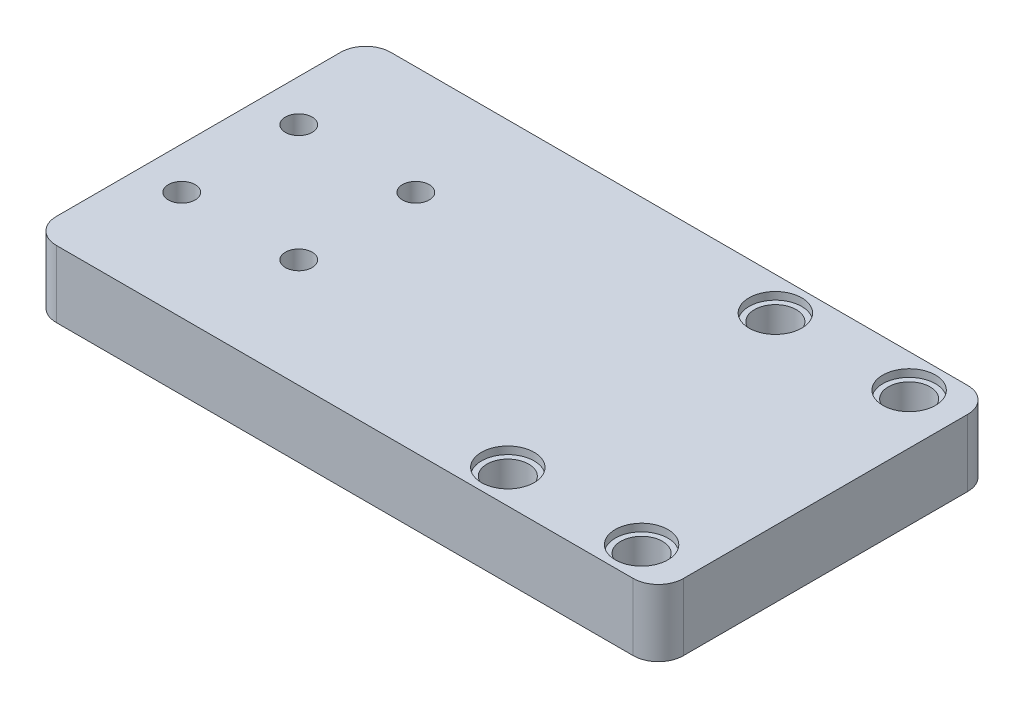
SolidWorks part; units mm, degrees
ref_plane "前视基准面" through (0, 0, 0) normal (0, 0, 1) x (1, 0, 0)
ref_plane "上视基准面" through (0, 0, 0) normal (0, 1, 0) x (1, 0, 0)
ref_plane "右视基准面" through (0, 0, 0) normal (1, 0, 0) x (0, 0, -1)
other "Configuration Table"
sketch "草图1" plane through (0, 0, 0) normal (0, 1, 0) x (1, 0, 0)
  line L1 (-37.5, -20) -> (37.5, -20)
  line L2 (-37.5, -20) -> (-37.5, 20)
  line L3 (-37.5, 20) -> (37.5, 20)
  line L4 (37.5, -20) -> (37.5, 20)
  line L5 (-37.5, -20) -> (37.5, 20) construction
  line L6 (-37.5, 20) -> (37.5, -20) construction
  point P0 (0, 0)
  dimension "D1" = 75
  dimension "D2" = 40
extrude "凸台-拉伸1" add sketch "草图1" along normal blind 8
sketch "草图2" plane through (0, 8, 0) normal (0, 1, 0) x (1, 0, 0)
  line L0 (-37.5, 20) -> (-37.5, -20) construction
  line L1 (-32.5, -7) -> (-18.5, -7) construction
  line L2 (-32.5, -7) -> (-32.5, 7) construction
  line L3 (-32.5, 7) -> (-18.5, 7) construction
  line L4 (-18.5, -7) -> (-18.5, 7) construction
  line L5 (-32.5, -7) -> (-18.5, 7) construction
  line L6 (-32.5, 7) -> (-18.5, -7) construction
  line L7 (31.5, -16) -> (15.5, -16) construction
  line L8 (31.5, -16) -> (31.5, 16) construction
  line L9 (31.5, 16) -> (15.5, 16) construction
  line L10 (15.5, -16) -> (15.5, 16) construction
  line L11 (31.5, -16) -> (15.5, 16) construction
  line L12 (31.5, 16) -> (15.5, -16) construction
  line L13 (-32.5, 7) -> (-18.5, 7) construction
  line L14 (-32.5, 7) -> (-32.5, -7) construction
  line L15 (15.5, 16) -> (31.5, 16) construction
  circle A0 centre (-32.5, 7) radius 1.6
  circle A1 centre (15.5, 16) radius 2.5
  circle A2 centre (-18.5, 7) radius 1.6
  circle A3 centre (-18.5, -7) radius 1.6
  circle A4 centre (-32.5, -7) radius 1.6
  circle A5 centre (31.5, 16) radius 2.5
  circle A6 centre (31.5, -16) radius 2.5
  circle A7 centre (15.5, -16) radius 2.5
  point P0 (-25.5, 0)
  point P2 (15.5, -15.299)
  point P5 (23.5, 0)
  point P15 (15.9941, -15.49)
  dimension "D6" = 3.2
  dimension "D10" = 5
  dimension "D11" = 2
  dimension "D1" = 14
  dimension "D2" = 34
  dimension "D3" = 32
  dimension "D4" = 16
  dimension "D5" = 5
  dimension "D9" = 14
  dimension "D13" = 16
  dimension "D7" = 2
  dimension "D8" = 2
  dimension "D12" = 2
extrude "切除-拉伸1" cut sketch "草图2" against normal blind 8
sketch "草图3" plane through (0, 8, 0) normal (0, 1, 0) x (1, 0, 0)
  circle A0 centre (15.5, 16) radius 3.15
  dimension "D1" = 6.3
extrude "切除-拉伸2" cut sketch "草图3" against normal blind 0.9
pattern_linear "阵列(线性)1" count 2 spacing 16 along (1, 0, 0) count 2 spacing 32 along (0, 0, 1) of "切除-拉伸2"
ref_plane "基准面1" through (0, 4, 0) normal (0, 1, 0) x (1, 0, 0)
mirror "镜向1" about plane through (0, 4, 0) normal (0, 1, 0) of "切除-拉伸2", "阵列(线性)1"
fillet "圆角1" radius 3 4 edges at (-37.5, 4, 20) (37.5, 4, 20) (-37.5, 4, -20) (37.5, 4, -20)
